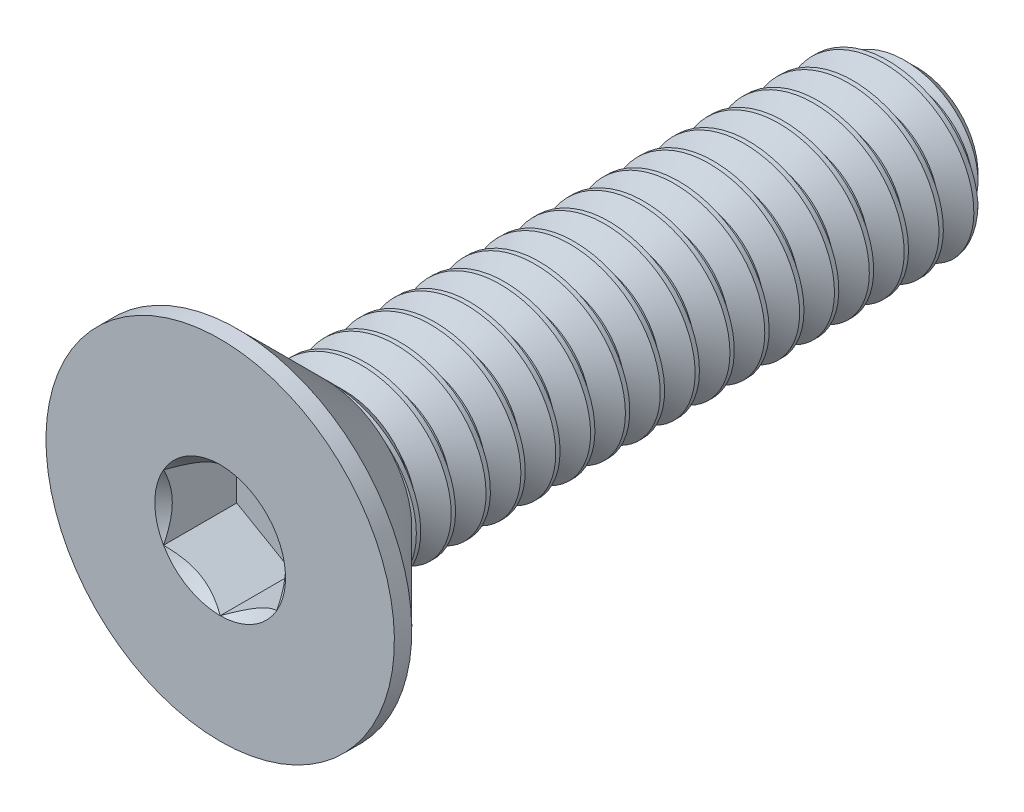
SolidWorks part; units mm, degrees
material "Brass"
ref_plane "Front" through (0, 0, 0) normal (0, 0, 1) x (1, 0, 0)
ref_plane "Top" through (0, 0, 0) normal (0, 1, 0) x (1, 0, 0)
ref_plane "Right" through (0, 0, 0) normal (1, 0, 0) x (0, 0, -1)
sketch "Sketch1" plane through (0, 0, 0) normal (1, 0, 0) x (0, 0, -1)
  line L0 (0, 2) -> (0.2, 2) construction
  line L1 (0.2, 2) -> (1.2, 1) construction
  line L2 (0, 1) -> (8, 1)
  line L3 (8, 1) -> (8, 0)
  line L4 (8, 0) -> (0, 0)
  line L5 (0, 0) -> (0, 2) construction
  line L6 (0, 2) -> (0, -2) construction
  line L7 (8, 1) -> (8, -1) construction
  line L8 (0, -2) -> (0.2, -2) construction
  line L9 (0.2, -2) -> (1.2, -1) construction
  line L11 (0, 1) -> (0, 0)
  line L12 (1.2, 1) -> (1.2, 0) construction
revolve "Revolve1" add sketch "Sketch1" angle 360 mid plane about L4
sketch "Sketch3" plane through (0, 0, -8) normal (0, 0, -1) x (-1, 0, 0)
  circle A0 centre (0, 0) radius 1
curve "Helix/Spiral1" pitch 0.4 height 8 radius 1 centre (0, 0, -8) axis (0, 0, 1) start towards (0, 1, 0)
sketch "Sketch2" plane through (0, 0, 0) normal (1, 0, 0) x (0, 0, -1)
  line L0 (8, 1) -> (8.35, 1)
  line L1 (8.35, 1) -> (8.2, 0.7402)
  line L2 (8.2, 0.7402) -> (8.15, 0.7402)
  line L3 (8.15, 0.7402) -> (8, 1)
  line L4 (8.075, 0.8701) -> (8.275, 0.8701) construction
  dimension "D1" = 60
  dimension "D2" = 0.05
  dimension "D3" = 0.2
chamfer "Chamfer1" distance 0.3 angle 45 1 edges at (0, 1, -8)
sweep "Cut-Sweep1" cut profiles "Sketch2" path "Helix/Spiral1" align with end faces yes
sketch "Sketch7" plane through (0, 0, 0) normal (1, 0, 0) x (0, 0, -1)
  line L0 (0, 2) -> (0.2, 2) construction
  line L1 (0.2, 2) -> (1.2, 1) construction
  line L2 (0, 2) -> (0.2, 2)
  line L3 (0.2, 2) -> (1.2, 1)
  line L4 (1.2, 1) -> (1.2, 0) construction
  line L5 (1.2, 1) -> (1.2, 0)
  line L7 (0, 0) -> (0, 2) construction
  line L8 (0, 0) -> (0, 2)
  line L9 (0, 0) -> (1.2, 0)
  line L10 (3.85, 0) -> (-3.85, 0) construction
revolve "Revolve2" add sketch "Sketch7" angle 360 mid plane about L9
ref_plane "Plane1" through (0, 0, -1.2) normal (0, 0, 1) x (1, 0, 0)
sketch "Sketch8" plane through (0, 0, -1.2) normal (0, 0, 1) x (1, 0, 0)
  circle A0 centre (0, 0) radius 1
extrude "Boss-Extrude1" add sketch "Sketch8" against normal through all draft 45
sketch "Sketch5" plane through (0, 0, 0) normal (0, 0, 1) x (1, 0, 0)
  line L1 (0.65, -0.3753) -> (0.65, 0.3753)
  line L2 (0.65, 0.3753) -> (0, 0.7506)
  line L3 (0, 0.7506) -> (-0.65, 0.3753)
  line L4 (-0.65, 0.3753) -> (-0.65, -0.3753)
  line L5 (-0.65, -0.3753) -> (0, -0.7506)
  line L6 (0, -0.7506) -> (0.65, -0.3753)
  circle A0 centre (0, 0) radius 0.65 construction
  dimension "Hex" = 1.3
extrude "Cut-Extrude2" cut sketch "Sketch5" against normal blind 0.84
sketch "Sketch6" plane through (0, 0, 0) normal (0, 0, 1) x (1, 0, 0)
  circle A0 centre (0, 0) radius 0.7506
extrude "Cut-Extrude3" cut sketch "Sketch6" against normal blind 0.84 draft 45
sketch "Sketch9" [suppressed] plane through (0, 0, -5.5) normal (0, 0, 1) x (1, 0, 0)
  circle A1 centre (0, 0) radius 5
  circle A2 centre (0, 0) radius 5
  point P0 (0, 5)
  dimension "D1" = 0
extrude "Boss-Extrude2" [suppressed] add sketch "Sketch9" against normal offset from surface (18.5 mm away) 26 up to face at (0, 0.7, -8)
fillet "Fillet1" [suppressed] radius 0.2
sketch "Sketch10" plane through (0, 0, 0) normal (1, 0, 0) x (0, 0, -1)
  line L0 (8, 1) -> (8, -1) construction
  point P0 (7.4, -1)
  dimension "D1" = 0.6
equation "\"D3@Helix/Spiral1\" = \"Lg@Sketch1\""
equation "\"D2@Sketch2\" = \"D4@Helix/Spiral1\" * .125"
equation "\"D3@Sketch2\" = \"D4@Helix/Spiral1\" * .5"
equation "\"D1@Chamfer1\" = \"D4@Helix/Spiral1\" * .75"
equation "\"D1@Cut-Extrude2\" = \"Head Ht@Sketch1\" * .7"
equation "\"D1@Sketch10\" = \"D4@Helix/Spiral1\" * 1.5"
equation "\"D1@Cut-Extrude3\" = \"D1@Cut-Extrude2\""
equation "\"D1@Fillet1\" = \"Dia@Sketch1\" * .1"
